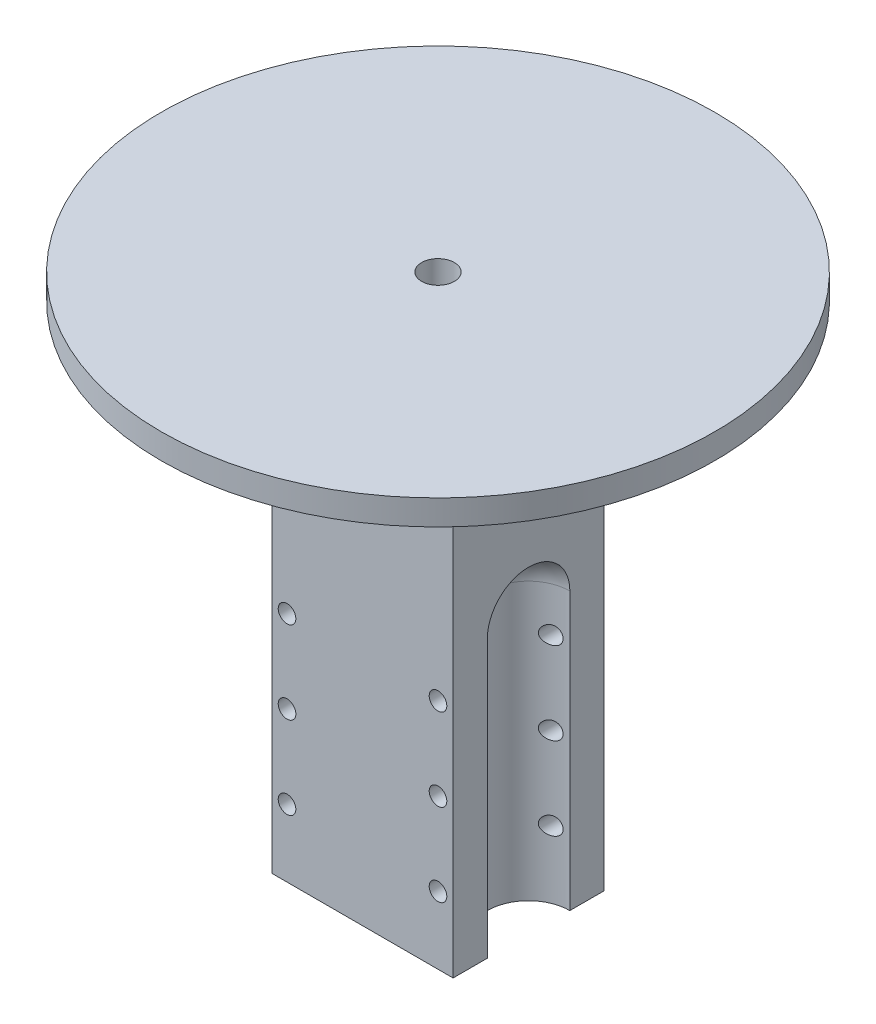
SolidWorks part; units mm, degrees
ref_plane "前视基准面" through (0, 0, 0) normal (0, 0, 1) x (1, 0, 0)
ref_plane "上视基准面" through (0, 0, 0) normal (0, 1, 0) x (1, 0, 0)
ref_plane "右视基准面" through (0, 0, 0) normal (1, 0, 0) x (0, 0, -1)
other "Configuration Table"
sketch "草图5" plane through (0, 0, 0) normal (0, 0, 1) x (1, 0, 0)
  line L1 (-18, 70) -> (0, 70)
  line L2 (-18, 70) -> (-18, -30)
  line L3 (-18, -30) -> (0, -30)
  line L4 (0, 70) -> (0, -30)
  dimension "D1" = 100
  dimension "D2" = 30
  dimension "D3" = 18
extrude "凸台-拉伸1" add sketch "草图5" along normal blind 15 and the other way blind 15
sketch "草图7" plane through (0, 0, 0) normal (0, 0, 1) x (1, 0, 0)
  line L0 (-18, -30) -> (0, -30) construction
  line L2 (-18, 70) -> (-18, -30) construction
  line L4 (-18, 8) -> (-18, -8)
  arc A1 (-18, -8) -> (-18, 8) centre (-18, 0) ccw
  dimension "D1" = 0
  dimension "D2" = 8
  dimension "D3" = 30
revolve "切除-旋转1" cut sketch "草图7" angle 360 about L4
pattern_linear "阵列(线性)1" count 2 spacing 16.1 along (0, 1, 0) count 2 spacing 16.1 along (0, -1, 0) of "切除-旋转1" pattern seed only yes
mirror "镜向2" about plane through (0, 0, 0) normal (1, 0, 0) of "凸台-拉伸1"
mirror "镜向3" about plane through (0, 0, 0) normal (1, 0, 0) of "切除-旋转1"
mirror "镜向4" about plane through (0, 0, 0) normal (1, 0, 0) of "阵列(线性)1"
sketch "草图9" plane through (0, 0, 0) normal (0, 0, 1) x (1, 0, 0)
  line L0 (18, 70) -> (-18, 70) construction
  line L1 (0, 70) -> (55, 70)
  line L2 (0, 70) -> (0, 75)
  line L3 (0, 75) -> (55, 75)
  line L4 (55, 70) -> (55, 75)
  dimension "D1" = 55
  dimension "D2" = 5
revolve "旋转1" add sketch "草图9" angle 360 about L2
sketch "草图12" plane through (0, 0, 0) normal (0, 1, 0) x (1, 0, 0)
  circle A0 centre (0, 0) radius 3.25
  dimension "D1" = 6.5
extrude "切除-拉伸1" cut sketch "草图12" against normal through all and the other way through all
sketch "草图15" plane through (0, 0, 0) normal (0, 1, 0) x (1, 0, 0)
  circle A0 centre (0, 0) radius 8
  dimension "D1" = 16
extrude "切除-拉伸4" cut sketch "草图15" against normal through all
sketch "草图17" plane through (0, 0, 0) normal (0, 0, 1) x (1, 0, 0)
  line L0 (-18, 25) -> (-9.8, 25)
  line L1 (-18, 70) -> (-18, -30) construction
  line L2 (-9.8, 25) -> (-9.8, -30)
  line L3 (-18, -30) -> (18, -30) construction
  line L4 (-9.8, -30) -> (-18, -30)
  line L5 (-18, -30) -> (-18, 25)
  dimension "D1" = 8.2
  dimension "D2" = 55
sketch "草图18" plane through (0, 0, 0) normal (0, 0, 1) x (1, 0, 0)
  line L0 (-18, 70) -> (-18, -30) construction
  line L1 (-18, 33.2) -> (-18, 16.8)
  line L2 (-18, -30) -> (18, -30) construction
  arc A0 (-18, 16.8) -> (-18, 33.2) centre (-18, 25) ccw
  dimension "D1" = 16.4
  dimension "D2" = 55
revolve "切除-旋转2" cut sketch "草图18" angle 360 about L1
revolve "切除-旋转3" cut sketch "草图17" angle 360 about L5
mirror "镜向5" about plane through (0, 0, 0) normal (1, 0, 0) of "切除-旋转2"
mirror "镜向6" about plane through (0, 0, 0) normal (1, 0, 0) of "切除-旋转3"
sketch "草图19" plane through (0, 0, 0) normal (0, 0, 1) x (1, 0, 0)
  line L0 (-18, 70) -> (-18, -30) construction
  line L1 (-18, -30) -> (18, -30) construction
  circle A0 centre (-15, 16.2) radius 1.75
  dimension "D1" = 3.5
  dimension "D2" = 3
  dimension "D3" = 46.2
extrude "切除-拉伸7" cut sketch "草图19" against normal through all and the other way through all
pattern_linear "阵列(线性)2" count 3 spacing 16.4 along (0, -1, 0) of "切除-拉伸7"
mirror "镜向7" about plane through (0, 0, 0) normal (1, 0, 0) of "阵列(线性)2"
